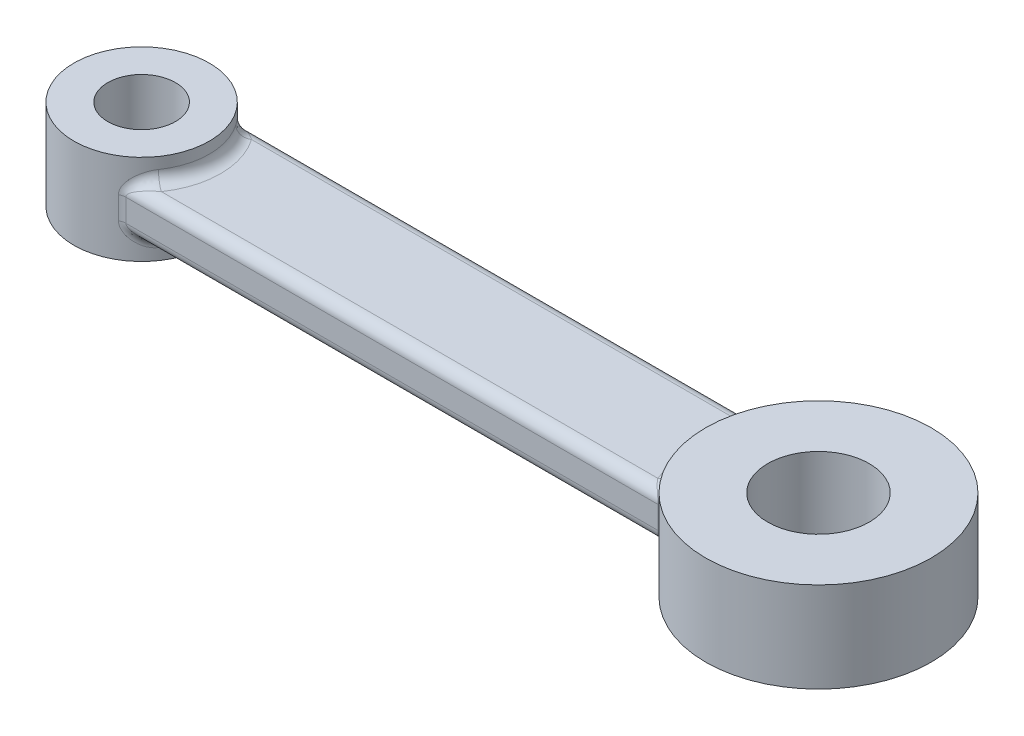
SolidWorks part; units mm, degrees
ref_plane "Front Plane" through (0, 0, 0) normal (0, 0, 1) x (1, 0, 0)
ref_plane "Top Plane" through (0, 0, 0) normal (0, 1, 0) x (1, 0, 0)
ref_plane "Right Plane" through (0, 0, 0) normal (1, 0, 0) x (0, 0, -1)
sketch "Sketch1" plane through (0, 0, 0) normal (0, 1, 0) x (1, 0, 0)
  line L1 (-15, -2.5) -> (15, -2.5)
  line L2 (-15, -2.5) -> (-15, 2.5)
  line L3 (-15, 2.5) -> (15, 2.5)
  line L4 (15, -2.5) -> (15, 2.5)
  line L5 (-15, -2.5) -> (15, 2.5) construction
  line L6 (-15, 2.5) -> (15, -2.5) construction
  point P0 (0, 0)
  dimension "D1" = 30
  dimension "D2" = 5
extrude "Boss-Extrude1" add sketch "Sketch1" along normal mid plane 2
sketch "Sketch2" plane through (0, 0, 0) normal (0, 1, 0) x (1, 0, 0)
  line L0 (-15, 2.5) -> (-15, -2.5) construction
  line L1 (15, -2.5) -> (15, 2.5) construction
  circle A0 centre (-15, 0) radius 3
  circle A1 centre (15, 0) radius 5
  point P9 (15, 0)
  point P10 (-15, 0)
  dimension "D1" = 6
  dimension "D2" = 10
extrude "Boss-Extrude2" add sketch "Sketch2" along normal mid plane 4
sketch "Sketch5" plane through (0, 2, 0) normal (0, 1, 0) x (1, 0, 0)
  circle A0 centre (15, 0) radius 2.25
  circle A1 centre (-15, 0) radius 1.5
  dimension "D1" = 3
  dimension "D2" = 4.5
extrude "Cut-Extrude1" cut sketch "Sketch5" against normal up to next
fillet "Fillet1" radius 0.5 12 edges at (-1.3359, 1, -2.5) (-1.3359, -1, -2.5) (-1.3359, -1, 2.5) (-1.3359, 1, 2.5) (-12, -1, 0) (10, -1, 0) (-13.3417, 0, 2.5) (-13.3417, 0, -2.5) (10.6699, 0, -2.5) (10.6699, 0, 2.5) (-12, 1, 0) (10, 1, 0)
